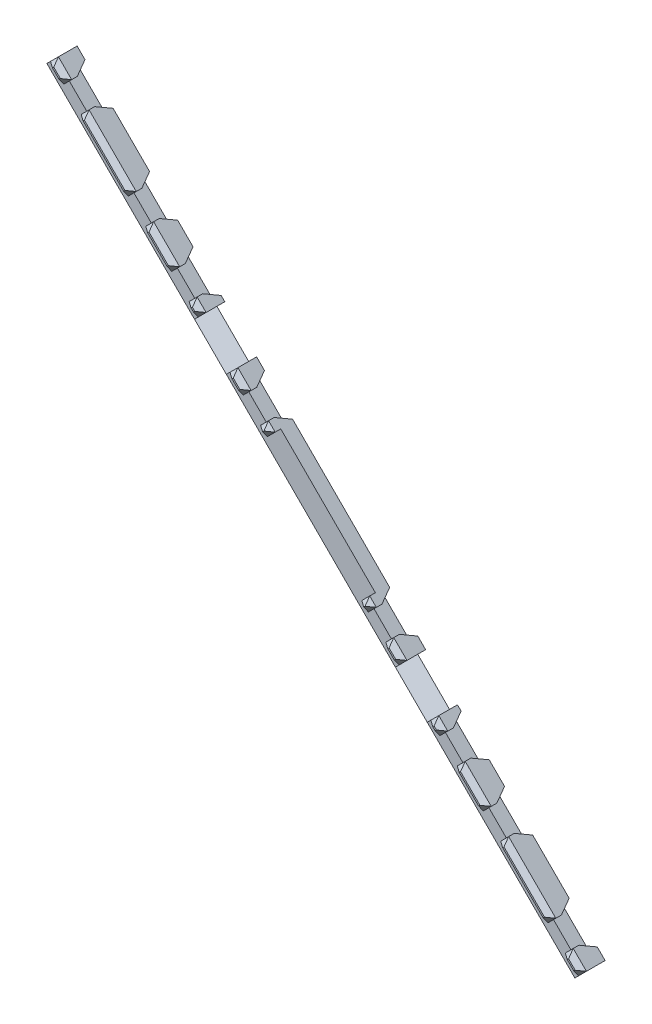
SolidWorks part; units mm, degrees
ref_plane "Ebene vorne" through (0, 0, 0) normal (0, 0, 1) x (1, 0, 0)
ref_plane "Ebene oben" through (0, 0, 0) normal (0, 1, 0) x (1, 0, 0)
ref_plane "Ebene rechts" through (0, 0, 0) normal (1, 0, 0) x (0, 0, -1)
sketch "Skizze1" plane through (0, 0, 0) normal (0, 0, 1) x (1, 0, 0)
  line L0 (0, 0) -> (0, -399.8)
  line L1 (0, 0) -> (-13, 0)
  line L2 (-13, 0) -> (-13, -10)
  line L3 (-13, -10) -> (-7, -10)
  line L4 (-7, -10) -> (-7, -23.2)
  line L5 (-7, -23.2) -> (-13, -23.2)
  line L6 (-13, -23.2) -> (-13, -58.9)
  line L7 (-13, -58.9) -> (-7, -58.9)
  line L8 (-7, -58.9) -> (-7, -72.1)
  line L9 (-7, -72.1) -> (-13, -72.1)
  line L10 (-13, -72.1) -> (-13, -91.8)
  line L11 (-13, -91.8) -> (-7, -91.8)
  line L12 (-7, -91.8) -> (-7, -105)
  line L13 (-7, -105) -> (-13, -105)
  line L14 (-13, -105) -> (-13, -111.8)
  line L15 (-13, -111.8) -> (-7, -111.8)
  line L16 (-10, -10) -> (-10, -14) construction
  line L17 (-10, -58.9) -> (-10, -62.9) construction
  line L18 (-10, -105) -> (-10, -101) construction
  line L19 (-7, -111.8) -> (-7, -135.9)
  line L20 (-7, -135.9) -> (-13, -135.9)
  line L21 (-13, -135.9) -> (-13, -145.9)
  line L22 (-13, -145.9) -> (-7, -145.9)
  line L23 (-7, -145.9) -> (-7, -159.1)
  line L24 (-7, -159.1) -> (-13, -159.1)
  line L25 (-13, -159.1) -> (-13, -240.7)
  line L26 (-10, -145.9) -> (-10, -149.9) construction
  line L27 (-13, -199.9) -> (0, -199.9) construction
  line L28 (-10, -253.9) -> (-10, -249.9) construction
  line L29 (-10, -294.8) -> (-10, -298.8) construction
  line L30 (-10, -340.9) -> (-10, -336.9) construction
  line L31 (-10, -389.8) -> (-10, -385.8) construction
  line L32 (-7, -240.7) -> (-13, -240.7)
  line L33 (-7, -253.9) -> (-7, -240.7)
  line L34 (-13, -253.9) -> (-7, -253.9)
  line L35 (-13, -263.9) -> (-13, -253.9)
  line L36 (-7, -263.9) -> (-13, -263.9)
  line L37 (-7, -288) -> (-7, -263.9)
  line L38 (-13, -288) -> (-7, -288)
  line L39 (-13, -294.8) -> (-13, -288)
  line L40 (-7, -294.8) -> (-13, -294.8)
  line L41 (-7, -308) -> (-7, -294.8)
  line L42 (-13, -308) -> (-7, -308)
  line L43 (-13, -327.7) -> (-13, -308)
  line L44 (-7, -327.7) -> (-13, -327.7)
  line L45 (-7, -340.9) -> (-7, -327.7)
  line L46 (-13, -340.9) -> (-7, -340.9)
  line L47 (-13, -376.6) -> (-13, -340.9)
  line L48 (-7, -376.6) -> (-13, -376.6)
  line L49 (-7, -389.8) -> (-7, -376.6)
  line L50 (-13, -389.8) -> (-7, -389.8)
  line L51 (-13, -399.8) -> (-13, -389.8)
  line L52 (0, -399.8) -> (-13, -399.8)
  point P3 (-10, -10)
  dimension "D1" = 10
  dimension "D2" = 13.2
  dimension "D3" = 6
  dimension "D4" = 10
  dimension "D5" = 4
  dimension "D6" = 48.9
  dimension "D7" = 38.1
  dimension "D8" = 10.8
  dimension "D9" = 48.9
  dimension "D10" = 50
extrude "Aufsatz-Linear austragen1" add sketch "Skizze1" along normal blind 7
sketch "Skizze2" plane through (0, 0, 0) normal (0, 0, -1) x (-1, 0, 0)
  line L0 (0, 0) -> (13, 0) construction
  line L1 (13, -10) -> (7, -10)
  line L2 (13, -10) -> (13, 0)
  line L3 (13, 0) -> (7, 0)
  line L4 (7, -10) -> (7, 0)
  line L5 (13, -159.1) -> (13, -240.7) construction
  line L6 (7, -23.2) -> (13, -23.2)
  line L7 (7, -23.2) -> (7, -58.9)
  line L8 (7, -58.9) -> (13, -58.9)
  line L9 (13, -23.2) -> (13, -58.9)
  line L10 (7, -72.1) -> (13, -72.1)
  line L11 (7, -72.1) -> (7, -91.8)
  line L12 (7, -91.8) -> (13, -91.8)
  line L13 (13, -72.1) -> (13, -91.8)
  line L14 (7, -105) -> (13, -105)
  line L15 (7, -105) -> (7, -111.8)
  line L16 (7, -111.8) -> (13, -111.8)
  line L17 (13, -105) -> (13, -111.8)
  line L18 (7, -135.9) -> (13, -135.9)
  line L19 (7, -135.9) -> (7, -145.9)
  line L20 (7, -145.9) -> (13, -145.9)
  line L21 (13, -135.9) -> (13, -145.9)
  line L22 (7, -159.1) -> (13, -159.1)
  line L23 (7, -159.1) -> (7, -164.1)
  line L24 (7, -164.1) -> (13, -164.1)
  line L25 (13, -159.1) -> (13, -164.1)
  line L27 (7, -240.7) -> (13, -240.7)
  line L28 (7, -240.7) -> (7, -235.7)
  line L29 (7, -235.7) -> (13, -235.7)
  line L30 (13, -240.7) -> (13, -235.7)
  line L31 (7, -253.9) -> (13, -253.9)
  line L32 (7, -253.9) -> (7, -263.9)
  line L33 (7, -263.9) -> (13, -263.9)
  line L34 (13, -253.9) -> (13, -263.9)
  line L35 (7, -288) -> (13, -288)
  line L36 (7, -288) -> (7, -294.8)
  line L37 (7, -294.8) -> (13, -294.8)
  line L38 (13, -288) -> (13, -294.8)
  line L39 (7, -308) -> (13, -308)
  line L40 (7, -308) -> (7, -327.7)
  line L41 (7, -327.7) -> (13, -327.7)
  line L42 (13, -308) -> (13, -327.7)
  line L43 (7, -340.9) -> (13, -340.9)
  line L44 (7, -340.9) -> (7, -376.6)
  line L45 (7, -376.6) -> (13, -376.6)
  line L46 (13, -340.9) -> (13, -376.6)
  line L47 (7, -389.8) -> (13, -389.8)
  line L48 (7, -389.8) -> (7, -399.8)
  line L49 (7, -399.8) -> (13, -399.8)
  line L50 (13, -389.8) -> (13, -399.8)
  dimension "D1" = 5
extrude "Aufsatz-Linear austragen2" add sketch "Skizze2" along normal blind 5.5
chamfer "Fase1" distance 7 angle 30 16 edges at (-10, -389.8, 7) (-10, -376.6, 7) (-10, -340.9, 7) (-10, -327.7, 7) (-10, -308, 7) (-10, -294.8, 7) (-10, -253.9, 7) (-10, -240.7, 7) (-10, -159.1, 7) (-10, -145.9, 7) (-10, -105, 7) (-10, -91.8, 7) (-10, -72.1, 7) (-10, -58.9, 7) (-10, -23.2, 7) (-10, -10, 7) first distance on face at (-9.4, -389.8, 0.6) first distance on face at (-9.4, -376.6, 0.6) first distance on face at (-9.4, -340.9, 0.6) first distance on face at (-9.4, -327.7, 0.6) first distance on face at (-9.4, -308, 0.6) first distance on face at (-9.4, -294.8, 0.6) first distance on face at (-9.4, -253.9, 0.6) first distance on face at (-9.4, -240.7, 0.6) first distance on face at (-9.4, -159.1, 0.6) first distance on face at (-9.4, -145.9, 0.6) first distance on face at (-9.4, -105, 0.6) first distance on face at (-9.4, -91.8, 0.6) first distance on face at (-9.4, -72.1, 0.6) first distance on face at (-9.4, -58.9, 0.6) first distance on face at (-9.4, -23.2, 0.6) first distance on face at (-9.4, -10, 0.6)
chamfer "Fase2" distance 7 angle 45 2 edges at (-7, -123.85, 0) (-7, -275.95, 0)
chamfer "Fase3" distance 2.5 angle 45 48 edges at (-10, -10, -5.5) (-10, -389.8, -5.5) (-13, -394.8, -5.5) (-10, -399.8, -5.5) (-7, -394.8, -5.5) (-10, -340.9, -5.5) (-13, -358.75, -5.5) (-10, -376.6, -5.5) (-7, -358.75, -5.5) (-10, -308, -5.5) (-13, -317.85, -5.5) (-10, -327.7, -5.5) (-7, -317.85, -5.5) (-10, -288, -5.5) (-13, -291.4, -5.5) (-10, -294.8, -5.5) (-7, -291.4, -5.5) (-10, -253.9, -5.5) (-13, -258.9, -5.5) (-10, -263.9, -5.5) (-7, -258.9, -5.5) (-10, -235.7, -5.5) (-13, -238.2, -5.5) (-10, -240.7, -5.5) (-7, -238.2, -5.5) (-10, -159.1, -5.5) (-13, -161.6, -5.5) (-10, -164.1, -5.5) (-7, -161.6, -5.5) (-10, -135.9, -5.5) (-13, -140.9, -5.5) (-10, -145.9, -5.5) (-7, -140.9, -5.5) (-10, -105, -5.5) (-13, -108.4, -5.5) (-10, -111.8, -5.5) (-7, -108.4, -5.5) (-7, -5, -5.5) (-10, 0, -5.5) (-13, -5, -5.5) (-10, -23.2, -5.5) (-13, -41.05, -5.5) (-10, -58.9, -5.5) (-7, -41.05, -5.5) (-10, -72.1, -5.5) (-13, -81.95, -5.5) (-10, -91.8, -5.5) (-7, -81.95, -5.5)
sketch "Skizze4" plane through (0, 0, 7) normal (0, 0, 1) x (1, 0, 0)
  line L0 (-6.5, -27.2415) -> (-6.5, -5.9585) construction
  line L8 (-6.5, -54.8585) -> (-6.5, -76.1415) construction
  line L9 (-6.5, -87.7585) -> (-6.5, -109.0415) construction
  line L10 (-6.5, -141.8585) -> (-6.5, -163.1415) construction
  line L11 (-6.5, -236.6585) -> (-6.5, -257.9415) construction
  line L12 (-6.5, -290.7585) -> (-6.5, -312.0415) construction
  line L13 (-6.5, -323.6585) -> (-6.5, -344.9415) construction
  line L14 (-6.5, -372.5585) -> (-6.5, -393.8415) construction
  line L15 (-7, -5.9585) -> (-7, -27.2415) construction
  line L16 (-7, -27.2415) -> (-13, -27.2415) construction
  line L17 (-13, -5.9585) -> (-7, -5.9585) construction
  line L18 (-13, -54.8585) -> (-7, -54.8585) construction
  line L19 (-7, -76.1415) -> (-13, -76.1415) construction
  line L20 (-13, -87.7585) -> (-7, -87.7585) construction
  line L21 (-7, -109.0415) -> (-13, -109.0415) construction
  line L22 (-13, -141.8585) -> (-7, -141.8585) construction
  line L23 (-7, -163.1415) -> (-13, -163.1415) construction
  line L24 (-13, -236.6585) -> (-7, -236.6585) construction
  line L25 (-7, -257.9415) -> (-13, -257.9415) construction
  line L26 (-13, -290.7585) -> (-7, -290.7585) construction
  line L27 (-7, -312.0415) -> (-13, -312.0415) construction
  line L28 (-13, -323.6585) -> (-7, -323.6585) construction
  line L29 (-7, -344.9415) -> (-13, -344.9415) construction
  line L30 (-13, -372.5585) -> (-7, -372.5585) construction
  line L31 (-7, -393.8415) -> (-13, -393.8415) construction
  text T0 "<b>M3</b>" font "Century Gothic" height in points 22
  text T1 "<b>M5</b>" font "Century Gothic" height in points 22
  text T2 "M3" font "Century Gothic" height in points 22
  text T3 "M3" font "Century Gothic" height in points 22
  text T4 "M3" font "Century Gothic" height in points 22
  text T5 "M3" font "Century Gothic" height in points 22
  text T6 "M5" font "Century Gothic" height in points 22
  text T7 "M3" font "Century Gothic" height in points 22
  dimension "D1" = 0.5
extrude "Schnitt-Linear austragen1" cut sketch "Skizze4" against normal blind 0.5
move or copy body "Körper-Verschieben/Kopieren1" bodies to move or copy 103 copy no rotation origin (-76.2234, -31.5728, 0.75) rotation axis (-0.3827, 0.9239, 0) rotation angle 180
